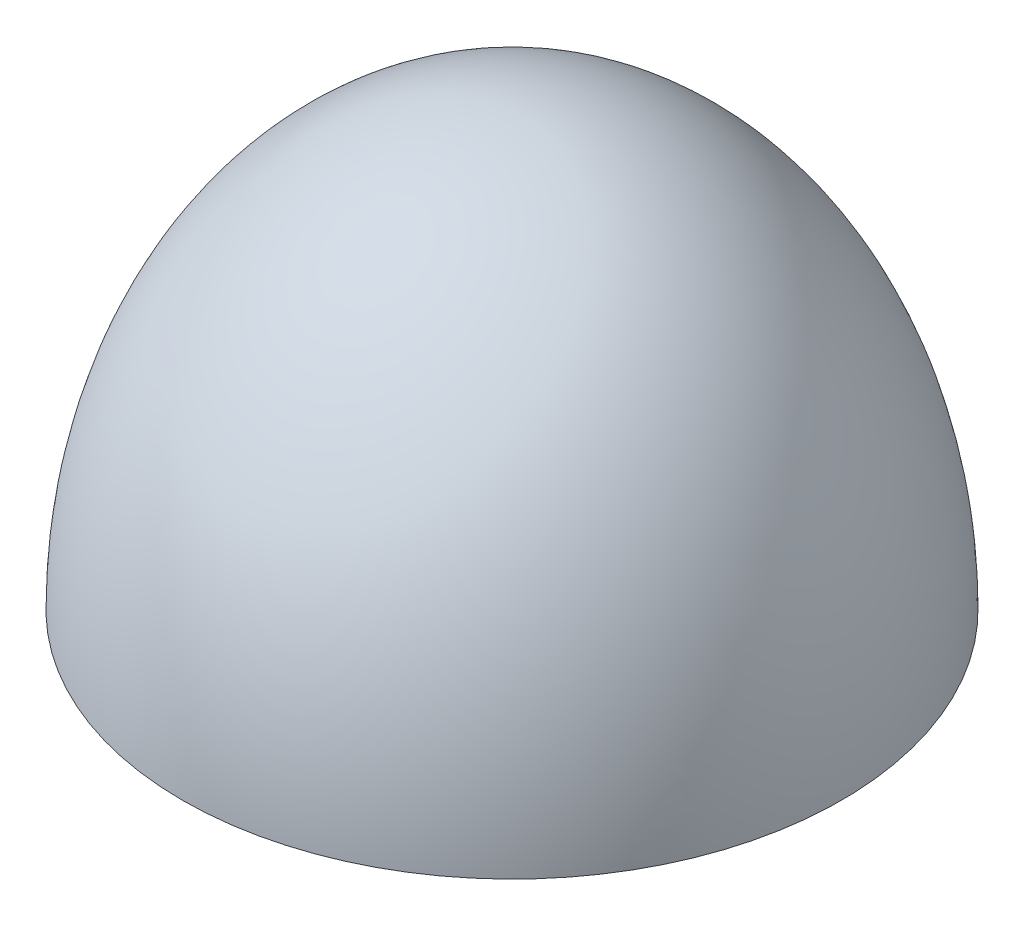
SolidWorks part; units mm, degrees
ref_plane "Front Plane" through (0, 0, 0) normal (0, 0, 1) x (1, 0, 0)
ref_plane "Top Plane" through (0, 0, 0) normal (0, 1, 0) x (1, 0, 0)
ref_plane "Right Plane" through (0, 0, 0) normal (1, 0, 0) x (0, 0, -1)
sketch "Sketch1" plane through (0, 0, 0) normal (1, 0, 0) x (0, 0, -1)
  line L2 (-2.5, 0) -> (-5, 0)
  line L5 (0, 4) -> (0, 6.5)
  line L6 (-2.5, 0) -> (-2.5, 4)
  line L7 (-2.5, 4) -> (0, 4)
  line L9 (0, 4) -> (0, 4873.7808) construction
  ellipse E0 centre (0, 0) end of major axis (0, 6.5) minor radius 5 (0, 6.5) -> (-5, 0) ccw
  point P5 (0, 6.5)
  dimension "D1" = 4
  dimension "D2" = 2.5
  dimension "D3" = 2.5
revolve "Revolve1" add sketch "Sketch1" angle 360 about L9
equation "\"2.5mmm\"=1.04938"
